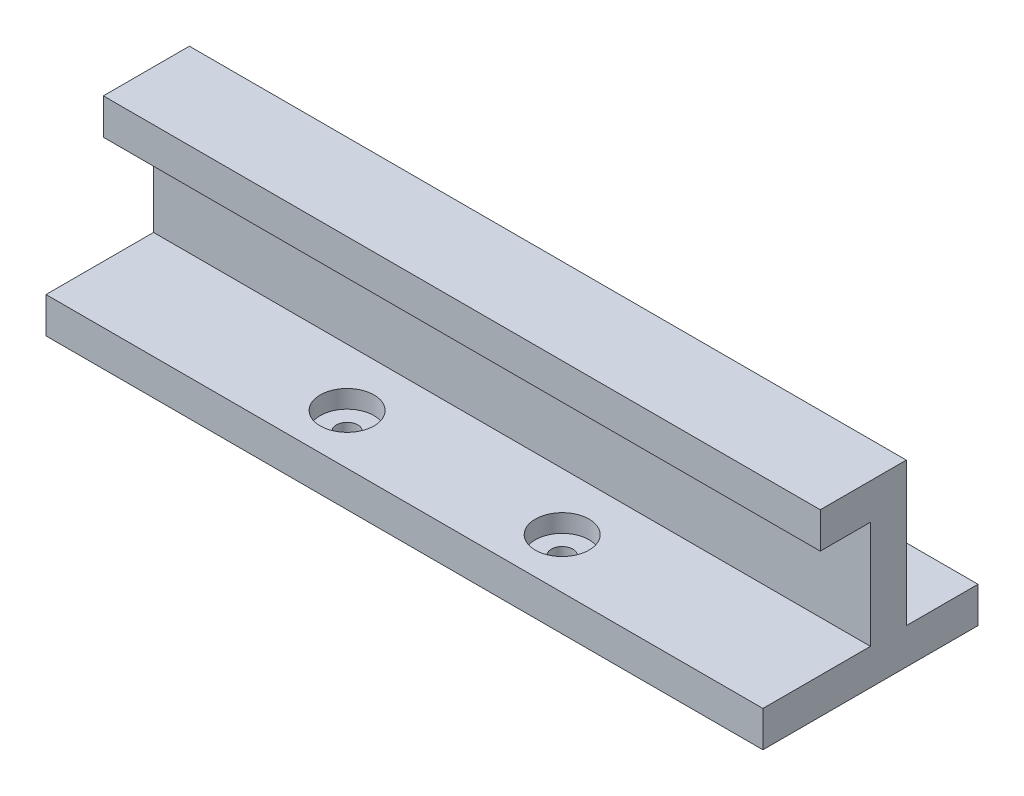
SolidWorks part; units mm, degrees
ref_plane "Front Plane" through (0, 0, 0) normal (0, 0, 1) x (1, 0, 0)
ref_plane "Top Plane" through (0, 0, 0) normal (0, 1, 0) x (1, 0, 0)
ref_plane "Right Plane" through (0, 0, 0) normal (1, 0, 0) x (0, 0, -1)
sketch "Sketch1" plane through (0, 0, 0) normal (0, 1, 0) x (1, 0, 0)
  line L0 (50, 20) -> (50, 0) construction
  line L1 (0, 0) -> (100, 0)
  line L2 (0, 0) -> (0, 20)
  line L3 (0, 20) -> (100, 20)
  line L4 (100, 0) -> (100, 20)
  circle A0 centre (35, 7) radius 1.5
  circle A1 centre (65, 7) radius 1.5
  dimension "D3" = 3
  dimension "D4" = 3
  dimension "D1" = 20
  dimension "D2" = 100
  dimension "D5" = 7
  dimension "D6" = 7
  dimension "D7" = 30
  dimension "D8" = 15
extrude "Extrude-Base" add sketch "Sketch1" along normal blind 5
sketch "Sketch2" plane through (0, 5, 0) normal (0, 1, 0) x (1, 0, 0)
  line L0 (100, 0) -> (100, 20) construction
  line L1 (0, 20) -> (100, 20)
  line L2 (0, 20) -> (0, 15)
  line L3 (0, 15) -> (100, 15)
  line L4 (100, 20) -> (100, 15)
  dimension "D1" = 5
extrude "Extrude-Vertical clamp" add sketch "Sketch2" along normal blind 20
sketch "Sketch3" plane through (0, 0, -15) normal (0, 0, 1) x (1, 0, 0)
  line L0 (100, 25) -> (100, 5) construction
  line L1 (0, 25) -> (100, 25)
  line L2 (0, 25) -> (0, 20)
  line L3 (0, 20) -> (100, 20)
  line L4 (100, 25) -> (100, 20)
  dimension "D1" = 5
extrude "Extrude-Clamp Roof" add sketch "Sketch3" along normal blind 7
sketch "Sketch5" plane through (0, 0, 0) normal (0, 1, 0) x (1, 0, 0)
  line L0 (100, 20) -> (100, 30)
  line L1 (100, 30) -> (0, 30)
  line L2 (0, 30) -> (0, 20)
  line L3 (0, 20) -> (100, 20)
  line L4 (50, 20) -> (50, 30) construction
  circle A0 centre (70, 25) radius 1.5
  circle A1 centre (30, 25) radius 1.5
  dimension "D2" = 20
  dimension "D6" = 3
  dimension "D7" = 3
  dimension "D1" = 10
  dimension "D3" = 20
  dimension "D4" = 5
  dimension "D5" = 5
extrude "Boss-Extrude4" add sketch "Sketch5" along normal blind 5
sketch "Sketch4" plane through (0, 5, 0) normal (0, 1, 0) x (1, 0, 0)
  circle A0 centre (35, 7) radius 3.75
  circle A1 centre (65, 7) radius 3.75
  circle A2 centre (35, 7) radius 1.5 construction
  circle A3 centre (65, 7) radius 1.5 construction
  circle A4 centre (30, 25) radius 3.75
  circle A5 centre (70, 25) radius 3.75
  dimension "D1" = 7.5
  dimension "D2" = 7.5
  dimension "D3" = 7.5
  dimension "D4" = 7.5
extrude "Cut-Extrude1" cut sketch "Sketch4" against normal blind 2.5
equation "\"screwInset\"=7.5"
equation "\"D1@Sketch4\"=\"screwInset\""
equation "\"D2@Sketch4\"=\"screwInset\""
equation "\"D3@Sketch4\"=\"screwInset\""
equation "\"D4@Sketch4\"=\"screwInset\""
